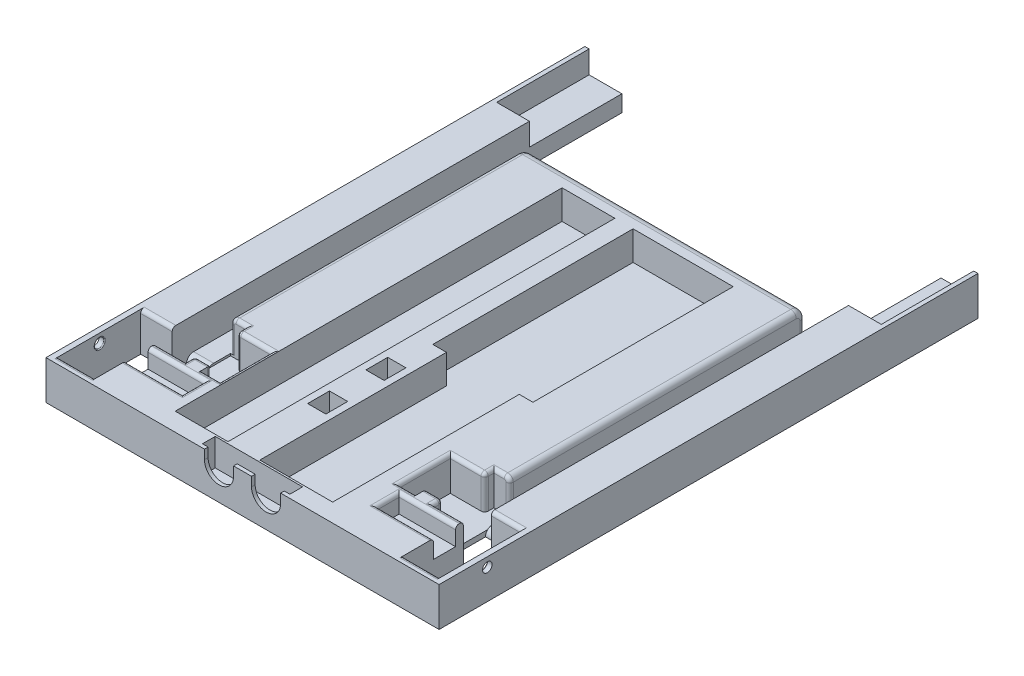
SolidWorks part; units mm, degrees
material "Custom Plastic"
ref_plane "Front Plane" through (0, 0, 0) normal (0, 0, 1) x (1, 0, 0)
ref_plane "Top Plane" through (0, 0, 0) normal (0, 1, 0) x (1, 0, 0)
ref_plane "Right Plane" through (0, 0, 0) normal (1, 0, 0) x (0, 0, -1)
sketch "Sketch1" plane through (0, 0, 0) normal (0, 1, 0) x (1, 0, 0)
  line L0 (-87.63, 296) -> (-87.63, 232.5)
  line L1 (-107.95, 0) -> (107.95, 0)
  line L2 (-107.95, 0) -> (-107.95, 296)
  line L3 (-107.95, 296) -> (-87.63, 296)
  line L4 (107.95, 0) -> (107.95, 296)
  line L5 (-87.63, 232.5) -> (87.63, 232.5)
  line L6 (87.63, 232.5) -> (87.63, 296)
  line L7 (87.63, 296) -> (107.95, 296)
  point P10 (0, 0)
  dimension "D1" = 296
  dimension "D2" = 215.9
  dimension "D3" = 20.32
  dimension "D4" = 63.5
extrude "Boss-Extrude1" add sketch "Sketch1" along normal blind 21.38
fillet "Fillet9" radius 5 1 edges at (0, 21.38, -232.5)
sketch "Sketch2" plane through (0, 21.38, 0) normal (0, 1, 0) x (1, 0, 0)
  line L0 (-107.95, 0) -> (107.95, 0) construction
  line L1 (-84.45, 32.55) -> (-53.45, 32.55)
  line L2 (-84.45, 32.55) -> (-84.45, 20.45)
  line L3 (-84.45, 20.45) -> (-53.45, 20.45)
  line L4 (-53.45, 32.55) -> (-53.45, 20.45)
  line L5 (-104.95, 49) -> (-84.45, 49)
  line L6 (-104.95, 49) -> (-104.95, 4)
  line L7 (-104.95, 4) -> (-84.45, 4)
  line L8 (-84.45, 49) -> (-84.45, 4)
  line L9 (-107.95, 29.25) -> (-104.95, 29.25)
  line L10 (-107.95, 29.25) -> (-107.95, 23.75)
  line L11 (-107.95, 23.75) -> (-104.95, 23.75)
  line L12 (-104.95, 29.25) -> (-104.95, 23.75)
  line L13 (-107.95, 296) -> (-107.95, 0) construction
  point P8 (-104.95, 26.5)
  point P9 (-84.45, 26.5)
  dimension "D1" = 12.1
  dimension "D2" = 31
  dimension "D3" = 20.5
  dimension "D4" = 45
  dimension "D5" = 5.5
  dimension "D6" = 3
  dimension "D7" = 4
  dimension "D8" = 0
extrude "Cut-Extrude1" cut sketch "Sketch2" against normal through all contours L8 L5 L6 L7 L2 region at (-94.7, 21.38, -26.5)
extrude "Cut-Extrude2" cut sketch "Sketch2<4>" against normal blind 10 contours L4 L1 L2 L3 region at (-68.95, 21.38, -26.5)
sketch "Sketch2<4>" plane through (0, 21.38, 0) normal (0, 1, 0) x (1, 0, 0) same geometry as "Sketch2"
sketch "Sketch8" plane through (-107.95, 0, 0) normal (-1, 0, 0) x (0, 0, 1)
  line L0 (-32.55, 21.38) -> (-20.45, 21.38) construction
  line L1 (-32.55, 21.38) -> (-20.45, 21.38) construction
  line L4 (-296, 0) -> (0, 0)
  line L5 (0, 0) -> (0, 21.38)
  line L6 (0, 21.38) -> (-296, 21.38)
  line L7 (-296, 21.38) -> (-296, 0)
  line L8 (-296, 0) -> (0, 0)
  line L9 (0, 0) -> (0, 21.38)
  line L10 (0, 21.38) -> (-296, 21.38)
  line L11 (-296, 21.38) -> (-296, 0)
  circle A0 centre (-26.5, 16.38) radius 2.625
  point P6 (-26.5, 21.38)
  dimension "D2" = 5.25
  dimension "D3" = 5
extrude "Cut-Extrude11" cut sketch "Sketch8" against normal up to next contours A0 region at (-107.95, 16.38, -26.5)
fillet "Fillet8" radius 0.5 1 edges at (-104.95, 16.38, -23.875)
fillet "Fillet2" radius 2 5 edges at (-94.7, 21.38, -4) (-94.7, 21.38, -49) (-68.95, 21.38, -20.45) (-53.45, 21.38, -26.5) (-68.95, 21.38, -32.55)
sketch "Sketch4" plane through (0, 0, 0) normal (0, -1, 0) x (1, 0, 0)
  line L1 (87.63, -232.5) -> (-87.63, -232.5) construction
  circle A0 centre (0, -226.5) radius 2.625
  point P2 (0, -210.3635)
  point P3 (0, 0)
  dimension "D1" = 5.25
  dimension "D2" = 6
extrude "Cut-Extrude4" cut sketch "Sketch4" against normal blind 6.12
sketch "Sketch5" plane through (0, 21.38, 0) normal (0, 1, 0) x (1, 0, 0)
  line L0 (87.63, 232.5) -> (-87.63, 232.5) construction
  line L1 (-87.63, 232.5) -> (-76.63, 232.5)
  line L2 (-87.63, 232.5) -> (-87.63, 36.78)
  line L3 (-87.63, 36.78) -> (-76.63, 36.78)
  line L4 (-76.63, 232.5) -> (-76.63, 36.78)
  line L6 (-87.63, 227.5) -> (-87.63, 296) construction
  line L7 (-87.63, 36.78) -> (-76.63, 36.78)
  line L8 (-87.63, 36.78) -> (-87.63, 56.78)
  line L9 (-87.63, 56.78) -> (-76.63, 56.78)
  line L10 (-76.63, 36.78) -> (-76.63, 56.78)
  point P6 (-82.13, 232.5)
  dimension "D2" = 11
  dimension "D3" = 195.72
  dimension "D4" = 20
extrude "Cut-Extrude5" cut sketch "Sketch5" against normal offset from surface (17.38 mm away) 4 contours L9 L4 L2 | L9 L3 L4 | L2 L1 L4 L3 | L8 L7 L10 L9 region at (-82.13, 21.38, -144.64) region at (-82.13, 21.38, -46.78) up to face at (0, 0, -229.125)
extrude "Cut-Extrude6" cut sketch "Sketch5<3>" against normal through all contours L9 L3 L4 | L8 L7 L10 L9 region at (-82.13, 21.38, -46.78)
sketch "Sketch5<3>" plane through (0, 21.38, 0) normal (0, 1, 0) x (1, 0, 0) same geometry as "Sketch5"
sketch "Sketch6" plane through (0, 21.38, 0) normal (0, 1, 0) x (1, 0, 0)
  line L1 (-76.63, 36.78) -> (-67.99, 36.78)
  line L2 (-76.63, 36.78) -> (-76.63, 64.98)
  line L3 (-67.99, 64.98) -> (-49.13, 64.98)
  line L4 (-49.13, 41.88) -> (-49.13, 64.98)
  line L5 (-84.45, 36.78) -> (-76.63, 36.78) construction
  line L6 (-76.63, 232.5) -> (-76.63, 56.78) construction
  line L7 (-76.63, 70.08) -> (-67.99, 70.08)
  line L8 (-76.63, 70.08) -> (-76.63, 64.98)
  line L10 (-67.99, 70.08) -> (-67.99, 64.98)
  line L14 (-49.13, 41.88) -> (-67.99, 41.88)
  line L15 (-67.99, 36.78) -> (-67.99, 41.88)
  dimension "D1" = 8.64
  dimension "D2" = 27.5
  dimension "D3" = 5.1
  dimension "D4" = 33.3
extrude "Cut-Extrude7" cut sketch "Sketch6" against normal offset from surface (18.52 mm away) 2.86 up to face at (-88.415, 0, -36.64)
sketch "Sketch7" plane through (0, 21.38, 0) normal (0, 1, 0) x (1, 0, 0)
  line L1 (-49.13, 41.88) -> (-59.13, 41.88)
  line L2 (-49.13, 41.88) -> (-49.13, 36.88)
  line L3 (-49.13, 36.88) -> (-59.13, 36.88)
  line L4 (-59.13, 41.88) -> (-59.13, 36.88)
  dimension "D1" = 5
  dimension "D2" = 10
extrude "Cut-Extrude8" cut sketch "Sketch7" against normal up to surface (17.38 mm away) up to face at (-81.03, 4, -129.728)
fillet "Fillet5" radius 4 1 edges at (-82.13, 4, -56.78)
fillet "Fillet6" radius 2 12 edges at (-76.22, 21.38, -36.78) (-54.13, 21.38, -36.88) (-67.99, 21.38, -39.33) (-63.56, 21.38, -41.88) (-67.99, 21.38, -67.53) (-72.31, 21.38, -70.08) (-49.13, 21.38, -50.93) (-58.56, 21.38, -64.98) (-59.13, 12.69, -41.88) (-67.99, 12.12, -41.88) (-67.99, 12.12, -64.98) (-76.63, 12.69, -70.08)
fillet "Fillet7" radius 3 4 edges at (-76.0442, 20.7942, -70.6658) (-76.63, 21.38, -149.79) (-76.63, 10.19, -232.5) (-76.63, 19.9155, -231.0355)
mirror "Mirror2" about plane through (0, 0, 0) normal (1, 0, 0) of "Fillet8", "Cut-Extrude11", "Fillet6", "Cut-Extrude8", "Cut-Extrude7", "Fillet5", "Fillet2", "Cut-Extrude2", "Cut-Extrude1", "Cut-Extrude5", "Cut-Extrude6", "Fillet7"
sketch "Sketch9" plane through (0, 21.38, 0) normal (0, 1, 0) x (1, 0, 0)
  line L0 (-87.63, 296) -> (-107.95, 296) construction
  line L1 (-105.63, 296) -> (-87.63, 296)
  line L2 (-105.63, 296) -> (-105.63, 245.2)
  line L3 (-105.63, 245.2) -> (-87.63, 245.2)
  line L4 (-87.63, 296) -> (-87.63, 245.2)
  line L5 (107.95, 296) -> (87.63, 296) construction
  line L6 (87.63, 296) -> (105.63, 296)
  line L7 (87.63, 296) -> (87.63, 245.2)
  line L8 (87.63, 245.2) -> (105.63, 245.2)
  line L9 (105.63, 296) -> (105.63, 245.2)
  line L10 (-87.63, 51) -> (-87.63, 296) construction
  line L11 (87.63, 296) -> (87.63, 51) construction
  dimension "D1" = 18
  dimension "D2" = 50.8
extrude "Cut-Extrude12" cut sketch "Sketch9" against normal offset from surface (12.33 mm away) 9.05 up to face at (-88.415, 0, -36.64)
sketch "Sketch10" plane through (0, 21.38, 0) normal (0, 1, 0) x (1, 0, 0)
  line L0 (-73.63, 232.5) -> (73.63, 232.5) construction
  line L1 (-18, 122.5) -> (-47, 122.5)
  line L2 (-18, 122.5) -> (-18, 222.5)
  line L3 (-18, 222.5) -> (-47, 222.5)
  line L4 (-47, 122.5) -> (-47, 222.5)
  line L5 (-47, 172.5) -> (47, 172.5) construction
  line L6 (47, 112.5) -> (-8, 112.5)
  line L7 (47, 112.5) -> (47, 222.5)
  line L8 (47, 222.5) -> (-8, 222.5)
  line L9 (-8, 112.5) -> (-8, 222.5)
  line L10 (-107.95, 0) -> (107.95, 0) construction
  line L11 (-47, 122.5) -> (-18, 122.5)
  line L12 (-47, 122.5) -> (-47, 10)
  line L13 (-47, 10) -> (-18, 10)
  line L14 (-18, 122.5) -> (-18, 10)
  line L16 (-0.5, 112.5) -> (39.5, 112.5)
  line L17 (-0.5, 112.5) -> (-0.5, 10)
  line L18 (-0.5, 10) -> (39.5, 10)
  line L19 (39.5, 112.5) -> (39.5, 10)
  point P4 (0, 172.5)
  point P22 (19.5, 112.5)
  point P24 (19.5, 10)
  dimension "D1" = 29
  dimension "D2" = 100
  dimension "D3" = 10
  dimension "D4" = 55
  dimension "D5" = 110
  dimension "D6" = 10
  dimension "D7" = 10
  dimension "D8" = 40
extrude "Cut-Extrude13" cut sketch "Sketch10" against normal blind 16 contours L14 L1 L12 L13 | L5 L4 L1 L2 | L19 L6 L17 L18 | L5 L9 L6 L7 | L4 L5 L2 L3 | L9 L5 L7 L8 region at (-32.5, 21.38, -66.25) region at (-32.5, 21.38, -147.5) region at (19.5, 21.38, -197.5) region at (19.5, 21.38, -142.5) region at (-32.5, 21.38, -197.5) region at (19.5, 21.38, -61.25)
sketch "Sketch11" plane through (0, 21.38, 0) normal (0, 1, 0) x (1, 0, 0)
  line L1 (-24, 9) -> (24, 9)
  line L2 (-24, 9) -> (-24, 2)
  line L3 (-24, 2) -> (24, 2)
  line L4 (24, 9) -> (24, 2)
  line L5 (-24, 9) -> (24, 2) construction
  line L6 (-24, 2) -> (24, 9) construction
  point P0 (0, 5.5)
  point P5 (0.1826, 5.1447)
  point P7 (0, 0)
  dimension "D1" = 7
  dimension "D2" = 48
  dimension "D3" = 2
extrude "Cut-Extrude14" cut sketch "Sketch11" against normal blind 15
sketch "Sketch12" plane through (0, 0, 0) normal (0, 0, 1) x (1, 0, 0)
  line L0 (-12.925, 16.38) -> (12.925, 16.38) construction
  line L1 (-20.925, 16.38) -> (-20.925, 21.38)
  line L2 (-20.925, 21.38) -> (-4.925, 21.38)
  line L3 (-4.925, 21.38) -> (-4.925, 16.38)
  line L4 (-107.95, 0) -> (107.95, 0)
  line L5 (107.95, 0) -> (107.95, 21.38)
  line L6 (107.95, 21.38) -> (-107.95, 21.38)
  line L7 (-107.95, 21.38) -> (-107.95, 0)
  line L8 (-107.95, 0) -> (107.95, 0)
  line L9 (107.95, 0) -> (107.95, 21.38)
  line L10 (107.95, 21.38) -> (-107.95, 21.38)
  line L11 (-107.95, 21.38) -> (-107.95, 0)
  line L12 (24, 21.38) -> (-24, 21.38)
  line L13 (-24, 21.38) -> (-24, 6.38)
  line L14 (-24, 6.38) -> (24, 6.38)
  line L15 (24, 6.38) -> (24, 21.38)
  line L16 (24, 21.38) -> (-24, 21.38) construction
  line L17 (-24, 21.38) -> (-24, 6.38) construction
  line L18 (-24, 6.38) -> (24, 6.38) construction
  line L19 (24, 6.38) -> (24, 21.38) construction
  line L20 (4.925, 16.38) -> (4.925, 21.38)
  line L21 (4.925, 21.38) -> (20.925, 21.38)
  line L22 (20.925, 21.38) -> (20.925, 16.38)
  arc A0 (-20.925, 16.38) -> (-4.925, 16.38) centre (-12.925, 16.38) ccw
  arc A1 (4.925, 16.38) -> (20.925, 16.38) centre (12.925, 16.38) ccw
  point P13 (0, 16.38)
  line M13 (107.95, 21.38) -> (-107.95, 21.38)
  dimension "D3" = 16
  dimension "D4" = 25.85
  dimension "D5" = 2
  dimension "D1" = 0
  dimension "D2" = 0
extrude "Cut-Extrude15" cut sketch "Sketch12" against normal up to surface (2 mm away) contours L1 A0 L3 M13 | L20 A1 L22 L10 region at (-12.925, 15.5971, 0) region at (12.925, 15.5971, 0) up to face at (0, 13.88, -2)
sketch "Sketch13" plane through (0, 21.38, 0) normal (0, 1, 0) x (1, 0, 0)
  line L0 (-18, 10) -> (-0.5, 10) construction
  line L1 (-14.25, 94) -> (-4.25, 94)
  line L2 (-14.25, 94) -> (-14.25, 82)
  line L3 (-14.25, 82) -> (-4.25, 82)
  line L4 (-4.25, 94) -> (-4.25, 82)
  line L5 (-14.25, 94) -> (-4.25, 82) construction
  line L6 (-14.25, 82) -> (-4.25, 94) construction
  line L7 (-14.25, 62) -> (-4.25, 62)
  line L8 (-14.25, 62) -> (-14.25, 50)
  line L9 (-14.25, 50) -> (-4.25, 50)
  line L10 (-4.25, 62) -> (-4.25, 50)
  line L11 (-14.25, 62) -> (-4.25, 50) construction
  line L12 (-14.25, 50) -> (-4.25, 62) construction
  line L13 (-0.5, 112.5) -> (-0.5, 10) construction
  line L14 (-18, 222.5) -> (-18, 10) construction
  line L15 (-0.5, 10) -> (39.5, 10) construction
  line L16 (20.925, 0) -> (107.95, 0) construction
  point P0 (-9.25, 88)
  point P5 (-18, 13.2701)
  point P6 (-9.25, 56)
  point P15 (-9.25, 10)
  point P18 (0, 0)
  point P19 (-0.5, 10)
  point P22 (-4.25, 35.2834)
  dimension "D1" = 12
  dimension "D2" = 10
  dimension "D3" = 50
  dimension "D4" = 20
extrude "Cut-Extrude16" cut sketch "Sketch13" against normal blind 10
equation "\"D1@Sketch1\"=8in+2in+42mm"
equation "\"D2@Sketch1\"=8.5in"
equation "\"D3@Sketch1\"=.8in"
equation "\"D4@Sketch1\"=2.5in"
equation "\"D1@Boss-Extrude1\"=26.38-5"
equation "\"D5@Sketch2\"=5mm+.5"
equation "\"D1@Sketch4\"=5+.25"
equation "\"D1@Cut-Extrude4\"=11.12-5"
equation "\"D1@Cut-Extrude7\"=4+5-6.14"
equation "\"D2@Sketch8\"=5+.25"
equation "\"D2@Sketch9\"=2in"
equation "\"D3@Sketch5\"=102.92mm+2in+42mm"
